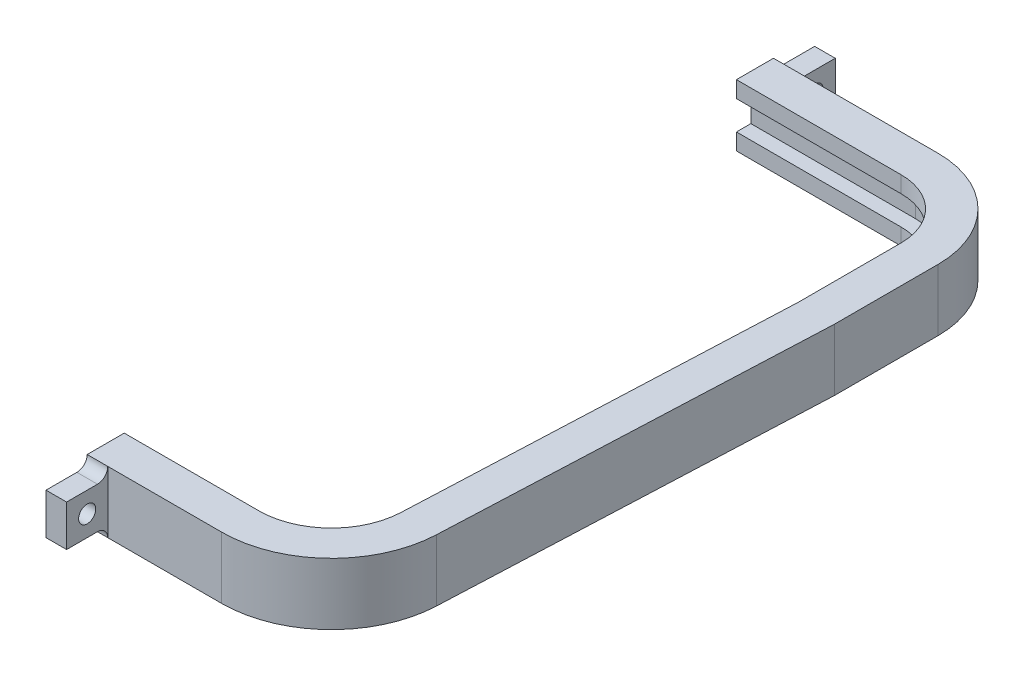
SolidWorks part; units mm, degrees
ref_plane "Front Plane" through (0, 0, 0) normal (0, 0, 1) x (1, 0, 0)
ref_plane "Top Plane" through (0, 0, 0) normal (0, 1, 0) x (1, 0, 0)
ref_plane "Right Plane" through (0, 0, 0) normal (1, 0, 0) x (0, 0, -1)
sketch "Sketch1" plane through (0, 0, 0) normal (0, 1, 0) x (1, 0, 0)
  line L0 (-32, 36) -> (-32, 21)
  line L1 (-24, 44) -> (24, 44)
  line L2 (32, 36) -> (32, 21)
  line L3 (-32, 21) -> (-29.5796, -34.4362)
  line L4 (-19.5891, -44) -> (19.5891, -44)
  line L5 (29.5796, -34.4362) -> (32, 21)
  line L6 (-24, 46.7) -> (24, 46.7)
  line L7 (34.7, 36) -> (34.7, 20.9411)
  line L8 (32.277, -34.554) -> (34.7, 20.9411)
  line L9 (-19.5891, -46.7) -> (19.5891, -46.7)
  line L10 (-34.7, 20.9411) -> (-32.277, -34.554)
  line L11 (-34.7, 36) -> (-34.7, 20.9411)
  line L12 (-24, 50) -> (24, 50)
  line L13 (38, 36) -> (38, 20.8691)
  line L14 (35.5739, -34.6979) -> (38, 20.8691)
  line L15 (-19.5891, -50) -> (19.5891, -50)
  line L16 (-38, 20.8691) -> (-35.5739, -34.6979)
  line L17 (-38, 36) -> (-38, 20.8691)
  line L18 (-32.6, 36) -> (-32.6, 20.9869)
  line L19 (-32.6, 20.9869) -> (-30.179, -34.4624)
  line L20 (-19.5891, -44.6) -> (19.5891, -44.6)
  line L21 (30.179, -34.4624) -> (32.6, 20.9869)
  line L22 (32.6, 36) -> (32.6, 20.9869)
  line L23 (-24, 44.6) -> (24, 44.6)
  arc A0 (-19.5891, -44) -> (-29.5796, -34.4362) centre (-19.5891, -34) cw
  arc A1 (29.5796, -34.4362) -> (19.5891, -44) centre (19.5891, -34) cw
  arc A2 (-24, 44) -> (-32, 36) centre (-24, 36) ccw
  arc A3 (32, 36) -> (24, 44) centre (24, 36) ccw
  arc A4 (34.7, 36) -> (24, 46.7) centre (24, 36) ccw
  arc A5 (32.277, -34.554) -> (19.5891, -46.7) centre (19.5891, -34) cw
  arc A6 (-19.5891, -46.7) -> (-32.277, -34.554) centre (-19.5891, -34) cw
  arc A7 (-24, 46.7) -> (-34.7, 36) centre (-24, 36) ccw
  arc A8 (38, 36) -> (24, 50) centre (24, 36) ccw
  arc A9 (35.5739, -34.6979) -> (19.5891, -50) centre (19.5891, -34) cw
  arc A10 (-19.5891, -50) -> (-35.5739, -34.6979) centre (-19.5891, -34) cw
  arc A11 (-24, 50) -> (-38, 36) centre (-24, 36) ccw
  arc A12 (-19.5891, -44.6) -> (-30.179, -34.4624) centre (-19.5891, -34) cw
  arc A13 (30.179, -34.4624) -> (19.5891, -44.6) centre (19.5891, -34) cw
  arc A14 (32.6, 36) -> (24, 44.6) centre (24, 36) ccw
  arc A15 (-24, 44.6) -> (-32.6, 36) centre (-24, 36) ccw
  point P0 (0, 0)
  dimension "D7" = 10
  dimension "D8" = 10
  dimension "D9" = 8
  dimension "D10" = 8
  dimension "D1" = 44
  dimension "D2" = 177.5
  dimension "D3" = 177.5
  dimension "D4" = 32
  dimension "D5" = 32
  dimension "D6" = 44
  dimension "D11" = 15
  dimension "D12" = 15
  dimension "D13" = 2.7
  dimension "D14" = 6
  dimension "D15" = 0.6
extrude "Boss-Extrude1" add sketch "Sketch1" along normal blind 4.5 and the other way blind 4.5 contours L12 A11 L17 L16 A10 L15 A9 L14 L13 A8 A7 L6 A4 L7 L8 A5 L9 A6 L10 L11 | L6 A7 L11 L10 A6 L9 A5 L8 L7 A4 A15 L23 A14 L22 L21 A13 L20 A12 L19 L18 region at (0, 0, -45.5364) region at (0, 0, -48.744)
extrude "Cut-Extrude1" cut sketch "Sketch1<3>" against normal blind 2.1 and the other way blind 2.1 contours L6 A4 L7 L8 A5 L9 A6 L10 L11 A7 | L1 A3 L2 L5 A1 L4 A0 L3 L0 A2
sketch "Sketch1<3>" plane through (0, 0, 0) normal (0, 1, 0) x (1, 0, 0) same geometry as "Sketch1"
sketch "Sketch2" plane through (0, 0, 0) normal (1, 0, 0) x (0, 0, -1)
  line L0 (-56, -3) -> (-50, -3)
  line L1 (-56, -3) -> (-56, 3)
  line L2 (-50, -3) -> (-50, 3)
  line L3 (-56, 3) -> (-50, 3)
  line L4 (-56, -3) -> (-50, 3) construction
  line L5 (-50, -3) -> (-56, 3) construction
  line L6 (50, -4.5) -> (50, 4.5) construction
  line L8 (-50, -4.5) -> (-50, 4.5) construction
  line L9 (50, -3) -> (56, -3)
  line L10 (50, -3) -> (50, 3)
  line L11 (56, -3) -> (56, 3)
  line L12 (50, 3) -> (56, 3)
  line L13 (50, -3) -> (56, 3) construction
  line L14 (56, -3) -> (50, 3) construction
  circle A0 centre (-53, 0) radius 1.25
  circle A1 centre (53, 0) radius 1.25
  point P1 (-53, 0)
  point P14 (53, 0)
  dimension "D1" = 2.5
  dimension "D4" = 2.5
  dimension "D2" = 6
  dimension "D3" = 6
  dimension "D5" = 6
  dimension "D6" = 6
extrude "Boss-Extrude2" add sketch "Sketch2" along normal blind 3 and the other way blind 3
fillet "Fillet2" radius 1.5 4 edges at (0, 3, -50) (0, -3, -50) (0, -3, 50) (0, 3, 50)
sketch "Sketch5" plane through (0, 0, 0) normal (1, 0, 0) x (0, 0, -1)
  line L1 (-60, -15) -> (60, -15)
  line L2 (-60, -15) -> (-60, 15)
  line L3 (-60, 15) -> (60, 15)
  line L4 (60, -15) -> (60, 15)
  line L5 (-60, -15) -> (60, 15) construction
  line L6 (-60, 15) -> (60, -15) construction
  point P0 (0, 0)
extrude "Cut-Extrude2" cut sketch "Sketch5" against normal through all
